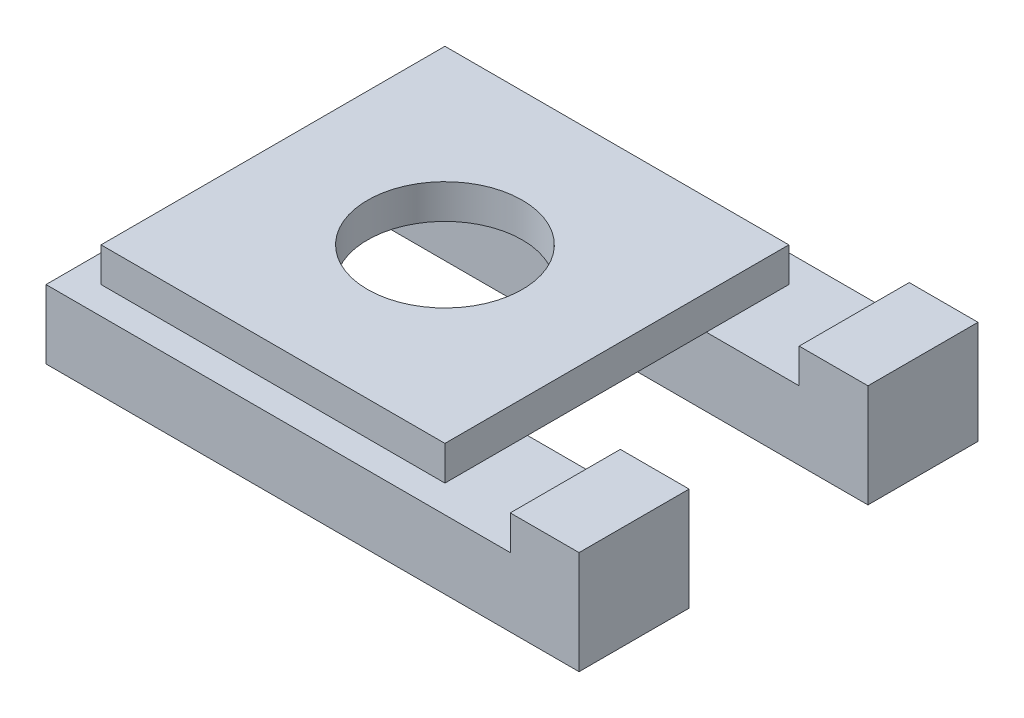
SolidWorks part; units mm, degrees
ref_plane "Front Plane" through (0, 0, 0) normal (0, 0, 1) x (1, 0, 0)
ref_plane "Top Plane" through (0, 0, 0) normal (0, 1, 0) x (1, 0, 0)
ref_plane "Right Plane" through (0, 0, 0) normal (1, 0, 0) x (0, 0, -1)
sketch "Sketch2" plane through (0, 0, 0) normal (0, 1, 0) x (1, 0, 0)
  line L0 (0, 0) -> (270.6265, 0) construction
  line L5 (-50, 50) -> (50, 50)
  line L6 (-50, 50) -> (-50, -50)
  line L7 (-50, -50) -> (50, -50)
  line L8 (50, 50) -> (50, -50)
  line L9 (270.6265, 0) -> (-283.2364, 0) construction
  line L10 (77, 58) -> (77, 26)
  line L11 (-58, 58) -> (97, 58)
  line L12 (-58, 58) -> (-58, 26)
  line L13 (-58, 26) -> (97, 26)
  line L14 (97, 58) -> (97, 26)
  line L15 (97, -58) -> (97, -26)
  line L16 (77, -58) -> (77, -26)
  line L17 (-58, -58) -> (97, -58)
  line L18 (-58, -26) -> (97, -26)
  line L19 (-58, -58) -> (-58, -26)
  circle A0 centre (0, 0) radius 22.5
  dimension "D1" = 45
  dimension "D2" = 100
  dimension "D3" = 100
  dimension "D4" = 50
  dimension "D5" = 50
  dimension "D6" = 32
  dimension "D7" = 8
  dimension "D8" = 155
  dimension "D9" = 8
  dimension "D10" = 20
extrude "Boss-Extrude1" add sketch "Sketch2" along normal blind 10 contours L6 L18 L8 L13 A0 | L6 L13 L8 L5 | L18 L6 L7 L8 | L14 L11 L10 L13 | L18 L16 L17 L15 region at (0, 0, -38) region at (0, 0, -24.8729) region at (0, 0, 38) region at (87, 0, -42) region at (87, 0, 42)
extrude "Boss-Extrude2" add sketch "Sketch2<4>" against normal blind 20 contours L19 L17 L16 L18 L8 L7 L6 | L12 L13 L6 L5 L8 L10 L11 | L18 L16 L17 L15 | L14 L11 L10 L13 region at (-51.3874, 0, -38) region at (-51.3874, 0, 38) region at (87, 0, -42) region at (87, 0, 42)
sketch "Sketch2<4>" plane through (0, 0, 0) normal (0, 1, 0) x (1, 0, 0) same geometry as "Sketch2"
extrude "Boss-Extrude3" add sketch "Sketch2<5>" against normal blind 20 contours L6 L13 L8 L5 | L18 L6 L7 L8 region at (0, 0, -38) region at (0, 0, 38)
sketch "Sketch2<5>" plane through (0, 0, 0) normal (0, 1, 0) x (1, 0, 0) same geometry as "Sketch2"
